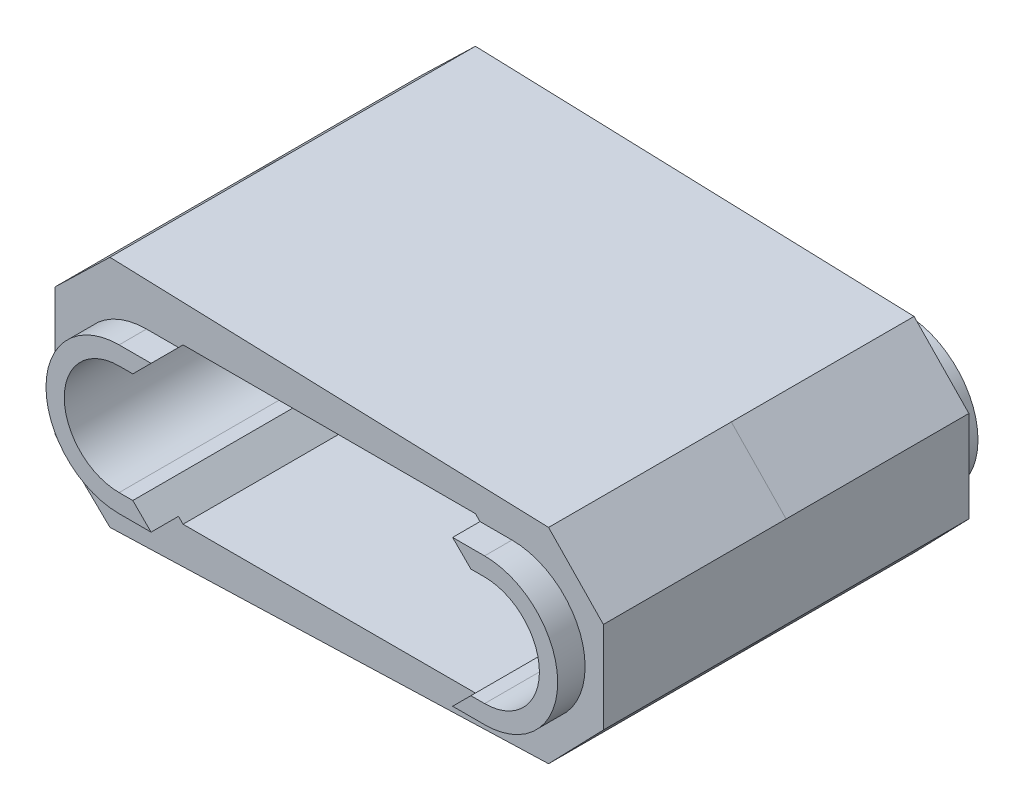
SolidWorks part; units mm, degrees
ref_plane "Front Plane" through (0, 0, 0) normal (0, 0, 1) x (1, 0, 0)
ref_plane "Top Plane" through (0, 0, 0) normal (0, 1, 0) x (1, 0, 0)
ref_plane "Right Plane" through (0, 0, 0) normal (1, 0, 0) x (0, 0, -1)
sketch "Sketch1" plane through (0, 0, 0) normal (0, 0, 1) x (1, 0, 0)
  line L0 (0, 0) -> (25, 0) construction
  line L1 (0, 6.5) -> (30, 5.5)
  line L2 (0, -6.5) -> (30, -5.5)
  line L3 (5, 0) -> (25, 0) construction
  line L4 (5, 3) -> (25, 3)
  line L5 (5, -3) -> (25, -3)
  line L6 (0, 6.5) -> (0, -6.5)
  line L7 (30, 5.5) -> (30, -5.5)
  line L8 (5, 4) -> (25, 4)
  line L9 (5, -4) -> (25, -4)
  arc A3 (5, 3) -> (5, -3) centre (5, 0) ccw
  arc A4 (25, -3) -> (25, 3) centre (25, 0) ccw
  arc A5 (25, -4) -> (25, 4) centre (25, 0) ccw
  arc A6 (5, 4) -> (5, -4) centre (5, 0) ccw
  point P3 (30, 0)
  point P7 (15, 0)
  point P15 (28, 0)
  point P20 (0, 0)
  point P23 (2, 0)
  dimension "D5" = 2
  dimension "D1" = 13
  dimension "D2" = 11
  dimension "D3" = 2
  dimension "D4" = 20
  dimension "D6" = 30
  dimension "D7" = 1
extrude "Boss-Extrude1" add sketch "Sketch1" along normal blind 10 contours L7 L1 L6 L2 A6 L8 A5 L9 | L8 A6 L9 A5 A4 L5 A3 L4 region at (14.9891, 5.6732, 0) region at (15, 3.7088, 0)
chamfer "Chamfer1" distance 3 distance2 3 4 edges at (0, -6.5, 5) (0, 6.5, 5) (30, -5.5, 5) (30, 5.5, 5)
extrude "Boss-Extrude2" add sketch "Sketch1<4>" against normal blind 1.5 contours L8 A6 L9 A5 A4 L5 A3 L4 region at (15, 3.7088, 0)
sketch "Sketch1<4>" plane through (0, 0, 0) normal (0, 0, 1) x (1, 0, 0) same geometry as "Sketch1"
mirror "Mirror1" about plane through (0, 0, 10) normal (0, 0, 1) of "Boss-Extrude1", "Chamfer1", "Boss-Extrude2"
sketch "Sketch2" plane through (0, 0, 21.5) normal (0, 0, 1) x (1, 0, 0)
  line L0 (5, 3) -> (25, 3) construction
  line L1 (7, 4.25) -> (23, 4.25)
  line L2 (7, 4.25) -> (7, -4.25)
  line L3 (7, -4.25) -> (23, -4.25)
  line L4 (23, 4.25) -> (23, -4.25)
  line L5 (7, 4.25) -> (23, -4.25) construction
  line L6 (7, -4.25) -> (23, 4.25) construction
  point P0 (15, 0)
  point P12 (15, 3)
  dimension "D1" = 8.5
  dimension "D2" = 16
extrude "Cut-Extrude1" cut sketch "Sketch2" against normal through all
chamfer "Chamfer2" distance 1.25 4 edges at (23, 3, 10) (23, -3, 10) (7, -3, 10) (7, 3, 10)
